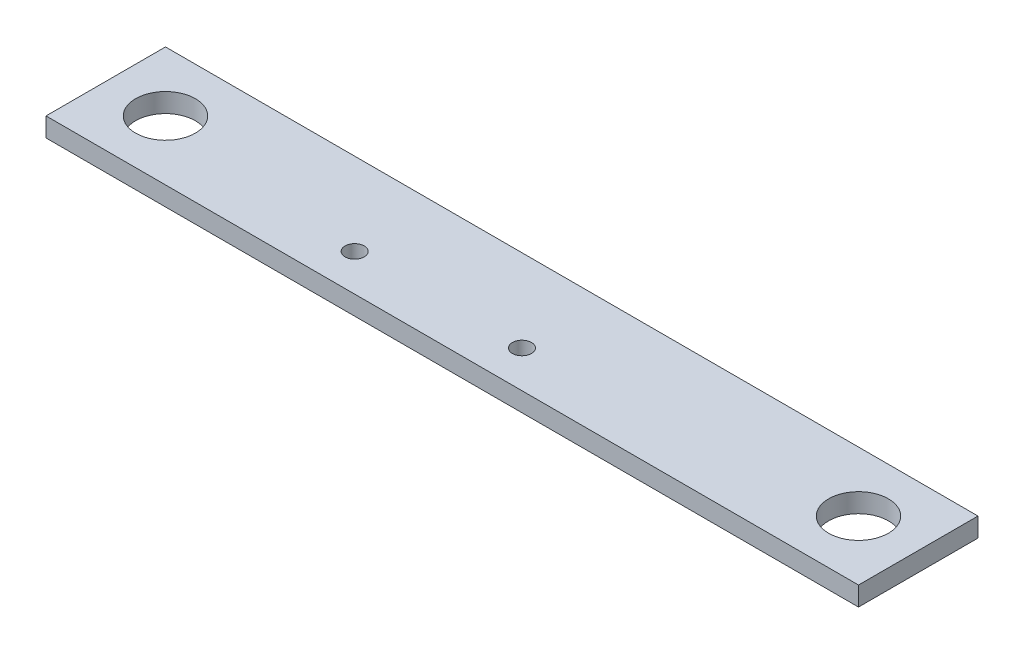
SolidWorks part; units mm, degrees
ref_plane "Front Plane" through (0, 0, 0) normal (0, 0, 1) x (1, 0, 0)
ref_plane "Top Plane" through (0, 0, 0) normal (0, 1, 0) x (1, 0, 0)
ref_plane "Right Plane" through (0, 0, 0) normal (1, 0, 0) x (0, 0, -1)
sketch "Sketch1" plane through (0, 0, 0) normal (0, 1, 0) x (1, 0, 0)
  line L1 (-85, 12.5) -> (85, 12.5)
  line L2 (-85, 12.5) -> (-85, -12.5)
  line L3 (-85, -12.5) -> (85, -12.5)
  line L4 (85, 12.5) -> (85, -12.5)
  line L5 (-85, 12.5) -> (85, -12.5) construction
  line L6 (-85, -12.5) -> (85, 12.5) construction
  circle A0 centre (-10.6801, 3.3392) radius 4.5
  circle A1 centre (-10.6585, -3.6607) radius 14
  circle A2 centre (-28.1585, -4.7634) radius 2
  circle A3 centre (6.8415, -4.7634) radius 2
  circle A4 centre (72.5, 0) radius 6.25
  point P0 (0, 0)
  point P17 (85, 0)
  dimension "D3" = 12.5
  dimension "D4" = 4
  dimension "D5" = 4
  dimension "D6" = 12.5
  dimension "D1" = 25
  dimension "D2" = 170
extrude "Boss-Extrude1" add sketch "Sketch1" along normal blind 4 contours A1 L3 L4 L1 L2 A4 A3 A2 | L3 A1 A0 | A0 region at (0, 0, -10.7817) region at (-10.6556, 0, 2.8007)
sketch "Sketch2" plane through (0, 4, 0) normal (0, 1, 0) x (1, 0, 0)
  line L0 (-85, 12.5) -> (-85, -12.5) construction
  circle A0 centre (-72.5, 0) radius 6.25
  circle A1 centre (-72.5, 0) radius 20 construction
  circle A2 centre (-42.5, 0) radius 10 construction
  dimension "D1" = 12.5
  dimension "D2" = 12.5
extrude "Cut-Extrude1" cut sketch "Sketch2" against normal through all
